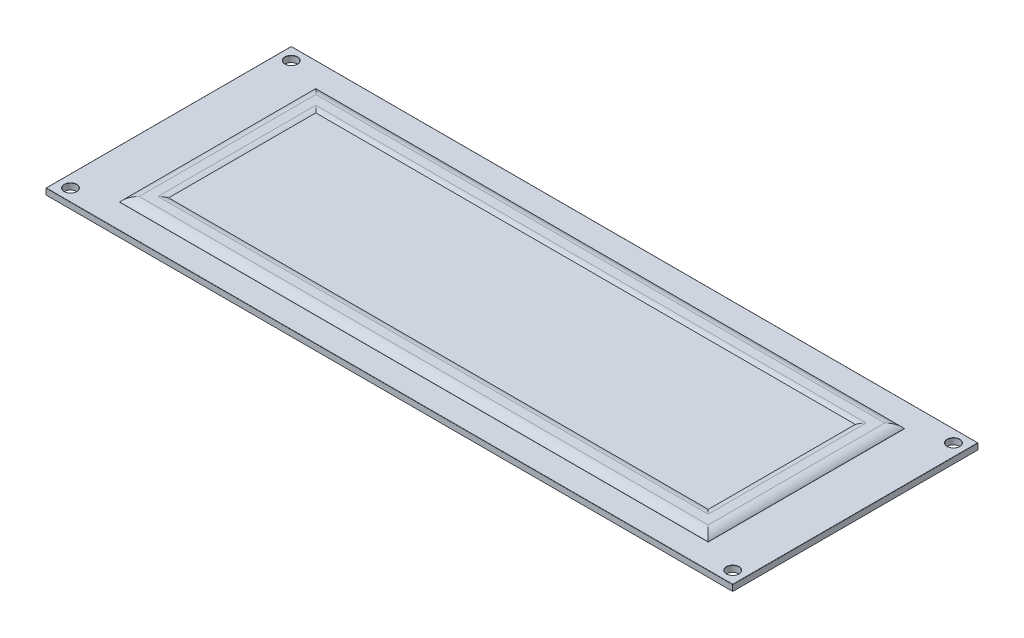
SolidWorks part; units mm, degrees
ref_plane "Front Plane" through (0, 0, 0) normal (0, 0, 1) x (1, 0, 0)
ref_plane "Top Plane" through (0, 0, 0) normal (0, 1, 0) x (1, 0, 0)
ref_plane "Right Plane" through (0, 0, 0) normal (1, 0, 0) x (0, 0, -1)
sketch "Sketch1" plane through (0, 0, 0) normal (0, 1, 0) x (1, 0, 0)
  line L1 (120.4411, 153.2938) -> (400.4411, 153.2938)
  line L2 (120.4411, 153.2938) -> (120.4411, 53.2938)
  line L3 (120.4411, 53.2938) -> (400.4411, 53.2938)
  line L4 (400.4411, 153.2938) -> (400.4411, 53.2938)
  dimension "D1" = 280
  dimension "D2" = 100
extrude "Boss-Extrude1" add sketch "Sketch1" along normal blind 2.5
sketch "Sketch2" plane through (0, 2.5, 0) normal (0, 1, 0) x (1, 0, 0)
  line L0 (120.4411, 53.2938) -> (400.4411, 53.2938) construction
  line L1 (140.4411, 143.2938) -> (380.4411, 143.2938)
  line L2 (140.4411, 143.2938) -> (140.4411, 63.2938)
  line L3 (140.4411, 63.2938) -> (380.4411, 63.2938)
  line L4 (380.4411, 143.2938) -> (380.4411, 63.2938)
  line L5 (400.4411, 153.2938) -> (120.4411, 153.2938) construction
  dimension "D1" = 20
  dimension "D2" = 20
  dimension "D3" = 10
  dimension "D4" = 10
extrude "Boss-Extrude2" add sketch "Sketch2" along normal blind 2
sketch "Sketch3" plane through (0, 4.5, 0) normal (0, 1, 0) x (1, 0, 0)
  line L0 (380.4411, 143.2938) -> (140.4411, 143.2938) construction
  line L1 (150.4411, 133.2938) -> (370.4411, 133.2938)
  line L2 (150.4411, 133.2938) -> (150.4411, 73.2938)
  line L3 (150.4411, 73.2938) -> (370.4411, 73.2938)
  line L4 (370.4411, 133.2938) -> (370.4411, 73.2938)
  line L5 (140.4411, 63.2938) -> (380.4411, 63.2938) construction
  dimension "D1" = 10
  dimension "D2" = 10
  dimension "D3" = 10
  dimension "D4" = 10
extrude "Cut-Extrude1" cut sketch "Sketch3" against normal blind 0.5
fillet "Fillet3" radius 5 8 edges at (260.4411, 4.5, -143.2938) (380.4411, 4.5, -103.2938) (260.4411, 4.5, -63.2938) (140.4411, 4.5, -103.2938) (260.4411, 4.5, -73.2938) (370.4411, 4.5, -103.2938) (260.4411, 4.5, -133.2938) (150.4411, 4.5, -103.2938)
sketch "Sketch4" plane through (0, 2.5, 0) normal (0, 1, 0) x (1, 0, 0)
  circle A0 centre (125.4411, 148.2938) radius 2.5
  circle A1 centre (395.4411, 148.2938) radius 2.5
  circle A2 centre (395.4411, 58.2938) radius 2.5
  circle A3 centre (125.4411, 58.2938) radius 2.5
  point P8 (0, 0)
  point P13 (373.7934, 152.7846)
  dimension "D1" = 5
  dimension "D2" = 5
  dimension "D3" = 5
  dimension "D4" = 5
  dimension "D5" = 5
  dimension "D6" = 5
  dimension "D7" = 5
  dimension "D8" = 5
  dimension "D9" = 5
  dimension "D10" = 5
  dimension "D11" = 5
  dimension "D12" = 5
extrude "Cut-Extrude2" cut sketch "Sketch4" against normal blind 30
fillet "Fillet4" radius 0.1 12 edges at (260.4411, 2.5, -153.2938) (400.4411, 2.5, -103.2938) (260.4411, 2.5, -53.2938) (120.4411, 2.5, -103.2938) (125.4411, 2.5, -145.7938) (395.4411, 2.5, -145.7938) (395.4411, 2.5, -55.7938) (125.4411, 2.5, -55.7938) (260.4411, 2.5, -63.2938) (380.4411, 2.5, -103.2938) (260.4411, 2.5, -143.2938) (140.4411, 2.5, -103.2938)
